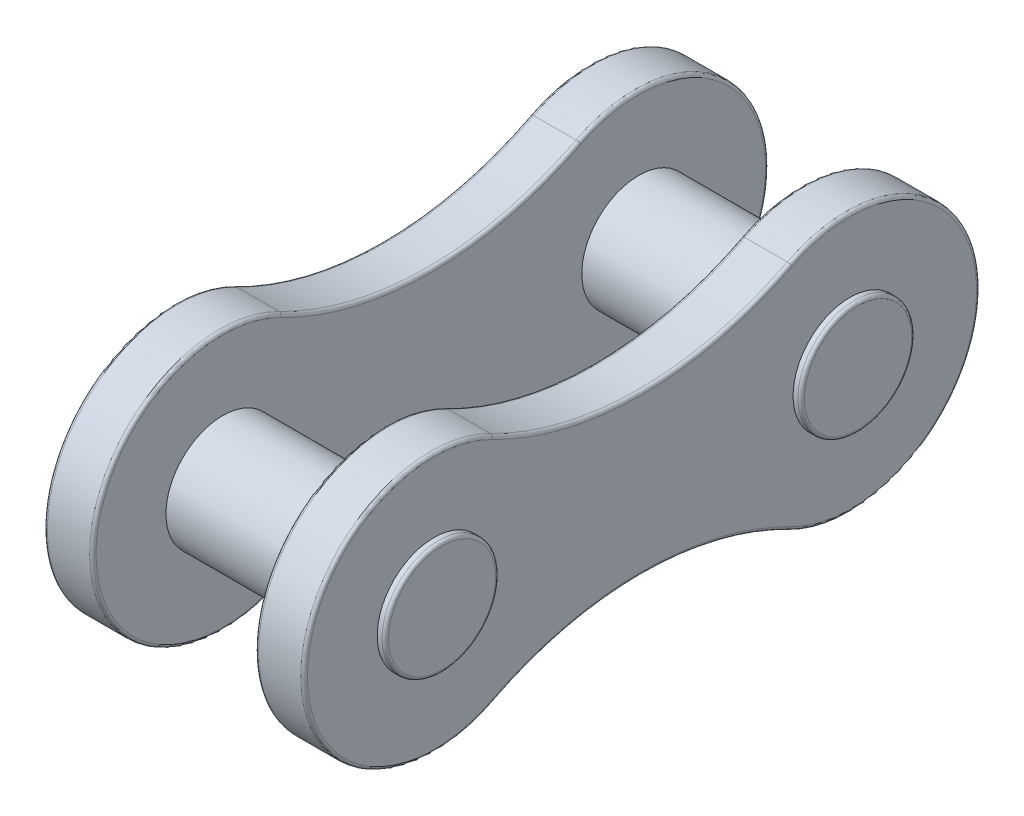
SolidWorks part; units mm, degrees
ref_plane "Front Plane" through (0, 0, 0) normal (0, 0, 1) x (1, 0, 0)
ref_plane "Top Plane" through (0, 0, 0) normal (0, 1, 0) x (1, 0, 0)
ref_plane "Right Plane" through (0, 0, 0) normal (1, 0, 0) x (0, 0, -1)
sketch "Sketch5" plane through (0, 0, 0) normal (1, 0, 0) x (0, 0, -1)
  line L0 (0, -1454.1638) -> (0, 3744.1855) construction
  line L1 (6.3985, 0) -> (-6.3985, 0) construction
  arc A0 (-4.5704, 3.5578) -> (-4.5704, -3.5578) centre (-6.3985, 0) ccw
  circle A1 centre (-6.3985, 0) radius 1.75
  circle A2 centre (6.3985, 0) radius 1.75
  arc A3 (4.5704, 3.5578) -> (4.5704, -3.5578) centre (6.3985, 0) cw
  arc A4 (-4.5704, 3.5578) -> (4.5704, 3.5578) centre (0, 12.4523) ccw
  arc A5 (-4.5704, -3.5578) -> (4.5704, -3.5578) centre (0, -12.4523) cw
  dimension "D1" = 8
  dimension "D2" = 3.5
  dimension "D4" = 10
  dimension "D3" = 12.797
extrude "Boss-Extrude2" add sketch "Sketch5" along normal blind 1.5 from offset 2.5
sketch "Sketch6" plane through (0, 0, 0) normal (1, 0, 0) x (0, 0, -1)
  circle A0 centre (6.3985, 0) radius 1.75 construction
  circle A1 centre (-6.3985, 0) radius 1.75 construction
  circle A2 centre (6.3985, 0) radius 1.75
  circle A3 centre (-6.3985, 0) radius 1.75
  arc A4 (-4.5704, 3.5578) -> (4.5704, 3.5578) centre (0, 12.4523) ccw
  arc A5 (-4.5704, 3.5578) -> (-4.5704, -3.5578) centre (-6.3985, 0) ccw
  arc A6 (4.5704, -3.5578) -> (-4.5704, -3.5578) centre (0, -12.4523) ccw
  arc A7 (4.5704, -3.5578) -> (4.5704, 3.5578) centre (6.3985, 0) ccw
  arc A8 (-4.5704, 3.5578) -> (4.5704, 3.5578) centre (0, 12.4523) ccw
  arc A9 (-4.5704, 3.5578) -> (-4.5704, -3.5578) centre (-6.3985, 0) ccw
  arc A10 (4.5704, -3.5578) -> (-4.5704, -3.5578) centre (0, -12.4523) ccw
  arc A11 (4.5704, -3.5578) -> (4.5704, 3.5578) centre (6.3985, 0) ccw
  dimension "D1" = 0
extrude "Boss-Extrude3" add sketch "Sketch6" against normal blind 1.5 from offset 2.5 separate body offset against normal yes
sketch "Sketch7" plane through (0, 0, 0) normal (1, 0, 0) x (0, 0, -1)
  circle A0 centre (6.3985, 0) radius 1.75 construction
  circle A1 centre (-6.3985, 0) radius 1.75 construction
  circle A2 centre (6.3985, 0) radius 1.75
  circle A3 centre (-6.3985, 0) radius 1.75
extrude "Boss-Extrude4" add sketch "Sketch7" along normal mid plane 8.5
fillet "Fillet1" radius 0.1 20 edges at (4, 0, -10.3985) (4, -2.4523, 0) (4, 0, 10.3985) (2.5, 0, -10.3985) (2.5, -2.4523, 0) (2.5, 0, 10.3985) (-4, 0, -10.3985) (-4, -2.4523, 0) (-4, 0, 10.3985) (-2.5, 0, -10.3985) (-2.5, -2.4523, 0) (-2.5, 0, 10.3985) (4, 2.4523, 0) (2.5, 2.4523, 0) (-4, 2.4523, 0) (-2.5, 2.4523, 0) (-4.25, 0, -8.1485) (-4.25, 0, 4.6485) (4.25, 0, -8.1485) (4.25, 0, 4.6485)
